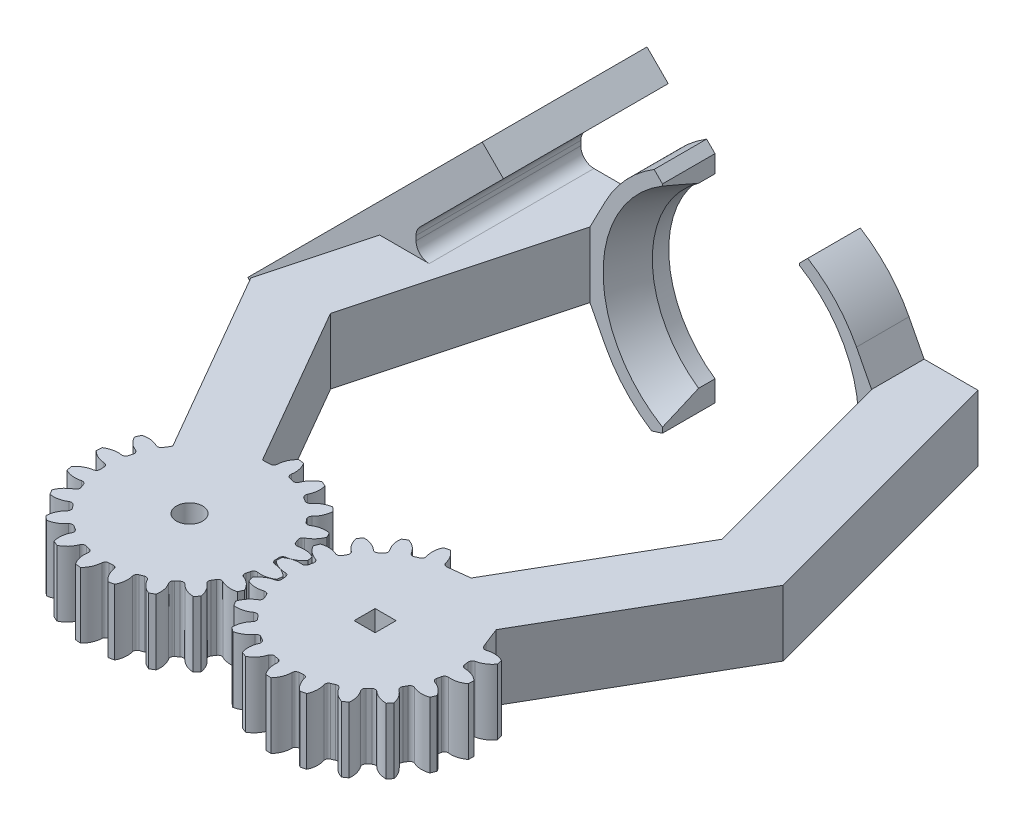
SolidWorks part; units mm, degrees
ref_plane "Front Plane" through (0, 0, 0) normal (0, 0, 1) x (1, 0, 0)
ref_plane "Top Plane" through (0, 0, 0) normal (0, 1, 0) x (1, 0, 0)
ref_plane "Right Plane" through (0, 0, 0) normal (1, 0, 0) x (0, 0, -1)
sketch "Sketch1" plane through (0, 0, 0) normal (0, 1, 0) x (1, 0, 0)
  line L0 (-1.5124, 12.6196) -> (-15.6699, 37.141)
  line L1 (-10.1727, 7.6196) -> (-25.6699, 34.4615)
  line L2 (29.9646, 12.9427) -> (43.9355, 37.141)
  line L3 (38.6794, 8.0371) -> (53.9355, 34.4615)
  line L4 (-13.3963, -7.7344) -> (-13.3913, -7.7315)
  line L5 (-13.1804, -8.0969) -> (-13.6023, -7.3661)
  line L6 (-10.3506, -11.4955) -> (-10.3468, -11.4912)
  line L7 (-10.0332, -11.7735) -> (-10.6603, -11.209)
  line L8 (-6.2917, -14.1314) -> (-6.2894, -14.1261)
  line L9 (-5.904, -14.2977) -> (-6.6748, -13.9546)
  line L10 (-1.6169, -15.384) -> (-1.6163, -15.3783)
  line L11 (-1.1968, -15.4224) -> (-2.0359, -15.3342)
  line L12 (3.2161, -15.1307) -> (3.2149, -15.1251)
  line L13 (3.6276, -15.0374) -> (2.8023, -15.2128)
  line L14 (7.7344, -13.3963) -> (7.7315, -13.3913)
  line L15 (8.0969, -13.1804) -> (7.3661, -13.6023)
  line L16 (11.4955, -10.3506) -> (11.4912, -10.3468)
  line L17 (11.7735, -10.0332) -> (11.209, -10.6603)
  line L18 (14.1314, -6.2917) -> (14.1261, -6.2894)
  line L19 (14.2977, -5.904) -> (13.9546, -6.6748)
  line L20 (15.384, -1.6169) -> (15.3783, -1.6163)
  line L21 (15.4224, -1.1968) -> (15.3342, -2.0359)
  line L22 (15.1307, 3.2161) -> (15.1251, 3.2149)
  line L23 (15.0374, 3.6276) -> (15.2128, 2.8023)
  line L24 (13.3963, 7.7344) -> (13.3913, 7.7315)
  line L25 (13.1804, 8.0969) -> (13.6023, 7.3661)
  line L26 (10.3506, 11.4955) -> (10.3468, 11.4912)
  line L27 (10.0332, 11.7735) -> (10.6603, 11.209)
  line L28 (6.2917, 14.1314) -> (6.2894, 14.1261)
  line L29 (5.904, 14.2977) -> (6.6748, 13.9546)
  line L30 (1.6169, 15.384) -> (1.6163, 15.3783)
  line L31 (1.1968, 15.4224) -> (2.0359, 15.3342)
  line L32 (-14.1314, 6.2917) -> (-14.1261, 6.2894)
  line L33 (-14.2977, 5.904) -> (-13.9546, 6.6748)
  line L34 (-15.384, 1.6169) -> (-15.3783, 1.6163)
  line L35 (-15.4224, 1.1968) -> (-15.3342, 2.0359)
  line L36 (-15.1307, -3.2161) -> (-15.1251, -3.2149)
  line L37 (-15.0374, -3.6276) -> (-15.2128, -2.8023)
  line L38 (-9.6435, -8.1965) -> (-10.0224, -7.7286)
  line L39 (-6.6387, -10.7754) -> (-7.1436, -10.4475)
  line L40 (-2.984, -12.2995) -> (-3.5655, -12.1436)
  line L41 (0.9628, -12.6196) -> (0.3616, -12.6511)
  line L42 (4.8154, -11.7044) -> (4.2533, -11.9202)
  line L43 (8.1965, -9.6435) -> (7.7286, -10.0224)
  line L44 (10.7754, -6.6387) -> (10.4475, -7.1436)
  line L45 (12.2995, -2.984) -> (12.1436, -3.5655)
  line L46 (12.6196, 0.9628) -> (12.6511, 0.3616)
  line L47 (11.7044, 4.8154) -> (11.9202, 4.2533)
  line L48 (9.6435, 8.1965) -> (10.0224, 7.7286)
  line L49 (6.6387, 10.7754) -> (7.1436, 10.4475)
  line L50 (2.984, 12.2995) -> (3.5655, 12.1436)
  line L51 (-0.9628, 12.6196) -> (-0.3616, 12.6511)
  line L52 (-10.7754, 6.6387) -> (-10.4475, 7.1436)
  line L53 (-12.2995, 2.984) -> (-12.1436, 3.5655)
  line L54 (-12.6196, -0.9628) -> (-12.6511, -0.3616)
  line L55 (-11.7044, -4.8154) -> (-11.9202, -4.2533)
  line L56 (43.7132, -0.8096) -> (43.7074, -0.8093)
  line L57 (43.6854, -1.2306) -> (43.7295, -0.388)
  line L58 (42.707, -5.5435) -> (42.7016, -5.5414)
  line L59 (42.5504, -5.9353) -> (42.8528, -5.1476)
  line L60 (40.2871, -9.7348) -> (40.2826, -9.7312)
  line L61 (40.0172, -10.059) -> (40.5481, -9.4033)
  line L62 (36.6905, -12.9732) -> (36.6874, -12.9684)
  line L63 (36.3336, -13.1981) -> (37.0412, -12.7386)
  line L64 (32.2693, -14.9417) -> (32.2678, -14.9361)
  line L65 (31.8603, -15.0453) -> (32.6753, -14.8269)
  line L66 (27.4561, -15.4476) -> (27.4564, -15.4418)
  line L67 (27.0351, -15.4197) -> (27.8777, -15.4639)
  line L68 (22.7221, -14.4413) -> (22.7242, -14.436)
  line L69 (22.3303, -14.2848) -> (23.1181, -14.5871)
  line L70 (18.5308, -12.0215) -> (18.5345, -12.017)
  line L71 (18.2066, -11.7515) -> (18.8623, -12.2825)
  line L72 (15.2925, -8.4249) -> (15.2973, -8.4218)
  line L73 (15.0675, -8.0679) -> (15.5271, -8.7756)
  line L74 (13.324, -4.0036) -> (13.3295, -4.0021)
  line L75 (13.2203, -3.5946) -> (13.4387, -4.4096)
  line L76 (12.8181, 0.8096) -> (12.8238, 0.8093)
  line L77 (12.8459, 1.2306) -> (12.8018, 0.388)
  line L78 (13.8243, 5.5435) -> (13.8297, 5.5414)
  line L79 (13.9809, 5.9353) -> (13.6785, 5.1476)
  line L80 (16.2442, 9.7348) -> (16.2486, 9.7312)
  line L81 (16.5141, 10.059) -> (15.9831, 9.4033)
  line L82 (19.8408, 12.9732) -> (19.8439, 12.9684)
  line L83 (20.1977, 13.1981) -> (19.4901, 12.7386)
  line L84 (24.262, 14.9417) -> (24.2635, 14.9361)
  line L85 (24.671, 15.0453) -> (23.856, 14.8269)
  line L86 (43.2073, 4.0036) -> (43.2018, 4.0021)
  line L87 (43.3109, 3.5946) -> (43.0926, 4.4096)
  line L88 (40.5792, -2.9251) -> (40.7044, -2.3362)
  line L89 (39.0727, -6.5871) -> (39.3737, -6.0656)
  line L90 (36.5082, -9.6042) -> (36.9557, -9.2013)
  line L91 (33.1369, -11.6812) -> (33.687, -11.4363)
  line L92 (29.2888, -12.6148) -> (29.8876, -12.5519)
  line L93 (25.3405, -12.3136) -> (25.9295, -12.4388)
  line L94 (21.6786, -10.807) -> (22.2, -11.1081)
  line L95 (18.6614, -8.2426) -> (19.0643, -8.69)
  line L96 (16.5844, -4.8713) -> (16.8293, -5.4213)
  line L97 (15.6508, -1.0232) -> (15.7138, -1.622)
  line L98 (15.9521, 2.9251) -> (15.8269, 2.3362)
  line L99 (17.4586, 6.5871) -> (17.1576, 6.0656)
  line L100 (20.0231, 9.6042) -> (19.5756, 9.2013)
  line L101 (23.3944, 11.6812) -> (22.8443, 11.4363)
  line L102 (27.2425, 12.6148) -> (26.6437, 12.5519)
  line L103 (39.9469, 4.8713) -> (39.702, 5.4213)
  line L104 (40.8805, 1.0232) -> (40.8175, 1.622)
  line L105 (27.2425, 12.6148) -> (29.9646, 12.9427)
  line L106 (39.702, 5.4213) -> (38.6794, 8.0371)
  line L107 (-10.4475, 7.1436) -> (-10.1727, 7.6196)
  line L108 (-0.9628, 12.6196) -> (-1.5124, 12.6196)
  line L109 (-15.6699, 37.141) -> (-5.3171, 75.778)
  line L110 (-5.3171, 75.778) -> (-14.9764, 78.3662)
  line L111 (-14.9764, 78.3662) -> (-26.4012, 35.7282)
  line L112 (-25.6699, 34.4615) -> (-26.4012, 35.7282)
  line L113 (43.9355, 37.141) -> (33.5828, 75.778)
  line L114 (33.5828, 75.778) -> (43.242, 78.3662)
  line L115 (43.242, 78.3662) -> (54.6668, 35.7282)
  line L116 (53.9355, 34.4615) -> (54.6668, 35.7282)
  circle A0 centre (0, 0) radius 2
  circle A1 centre (28.2656, 0) radius 2
  arc A2 (-13.1804, -8.0969) -> (-10.7748, -7.6007) centre (-12.61, -4.7824) ccw
  arc A3 (-10.0224, -7.7286) -> (-10.7748, -7.6007) centre (-10.4679, -8.0721) ccw
  arc A4 (-11.9698, -5.5309) -> (-13.6023, -7.3661) centre (-10.4467, -8.5294) ccw
  arc A5 (-11.9698, -5.5309) -> (-11.7044, -4.8154) centre (-12.2246, -5.0294) ccw
  arc A6 (-10.0332, -11.7735) -> (-7.8987, -10.5583) centre (-10.515, -8.4451) ccw
  arc A7 (-7.1436, -10.4475) -> (-7.8987, -10.5583) centre (-7.4611, -10.9118) ccw
  arc A8 (-9.6749, -8.9591) -> (-10.6603, -11.209) centre (-7.2997, -11.3401) ccw
  arc A9 (-9.6749, -8.9591) -> (-9.6435, -8.1965) centre (-10.0721, -8.5608) ccw
  arc A10 (-5.904, -14.2977) -> (-4.2494, -12.4824) centre (-7.3907, -11.281) ccw
  arc A11 (-3.5655, -12.1436) -> (-4.2494, -12.4824) centre (-3.724, -12.6833) ccw
  arc A12 (-6.4328, -11.5103) -> (-6.6748, -13.9546) centre (-3.4381, -13.0408) ccw
  arc A13 (-6.4328, -11.5103) -> (-6.6387, -10.7754) centre (-6.9337, -11.2543) ccw
  arc A14 (-1.1968, -15.4224) -> (-0.1841, -13.1846) centre (-3.5429, -13.0127) ccw
  arc A15 (0.3616, -12.6511) -> (-0.1841, -13.1846) centre (0.3776, -13.2134) ccw
  arc A16 (-2.5611, -12.9348) -> (-2.0359, -15.3342) centre (0.76, -13.465) ccw
  arc A17 (-2.5611, -12.9348) -> (-2.984, -12.2995) centre (-3.1166, -12.8461) ccw
  arc A18 (3.6276, -15.0374) -> (3.8991, -12.5962) centre (0.6517, -13.4707) ccw
  arc A19 (4.2533, -11.9202) -> (3.8991, -12.5962) centre (4.4423, -12.45) ccw
  arc A20 (1.5613, -13.0931) -> (2.8023, -15.2128) centre (4.8837, -12.5711) ccw
  arc A21 (1.5613, -13.0931) -> (0.9628, -12.6196) centre (1.0056, -13.1804) ccw
  arc A22 (8.0969, -13.1804) -> (7.6007, -10.7748) centre (4.7824, -12.61) ccw
  arc A23 (7.7286, -10.0224) -> (7.6007, -10.7748) centre (8.0721, -10.4679) ccw
  arc A24 (5.5309, -11.9698) -> (7.3661, -13.6023) centre (8.5294, -10.4467) ccw
  arc A25 (5.5309, -11.9698) -> (4.8154, -11.7044) centre (5.0294, -12.2246) ccw
  arc A26 (11.7735, -10.0332) -> (10.5583, -7.8987) centre (8.4451, -10.515) ccw
  arc A27 (10.4475, -7.1436) -> (10.5583, -7.8987) centre (10.9118, -7.4611) ccw
  arc A28 (8.9591, -9.6749) -> (11.209, -10.6603) centre (11.3401, -7.2997) ccw
  arc A29 (8.9591, -9.6749) -> (8.1965, -9.6435) centre (8.5608, -10.0721) ccw
  arc A30 (14.2977, -5.904) -> (12.4824, -4.2494) centre (11.281, -7.3907) ccw
  arc A31 (12.1436, -3.5655) -> (12.4824, -4.2494) centre (12.6833, -3.724) ccw
  arc A32 (11.5103, -6.4328) -> (13.9546, -6.6748) centre (13.0408, -3.4381) ccw
  arc A33 (11.5103, -6.4328) -> (10.7754, -6.6387) centre (11.2543, -6.9337) ccw
  arc A34 (15.4224, -1.1968) -> (13.1846, -0.1841) centre (13.0127, -3.5429) ccw
  arc A35 (12.6511, 0.3616) -> (13.1846, -0.1841) centre (13.2134, 0.3776) ccw
  arc A36 (12.9348, -2.5611) -> (15.3342, -2.0359) centre (13.465, 0.76) ccw
  arc A37 (12.9348, -2.5611) -> (12.2995, -2.984) centre (12.8461, -3.1166) ccw
  arc A38 (15.0374, 3.6276) -> (12.5962, 3.8991) centre (13.4707, 0.6517) ccw
  arc A39 (11.9202, 4.2533) -> (12.5962, 3.8991) centre (12.45, 4.4423) ccw
  arc A40 (13.0931, 1.5613) -> (15.2128, 2.8023) centre (12.5711, 4.8837) ccw
  arc A41 (13.0931, 1.5613) -> (12.6196, 0.9628) centre (13.1804, 1.0056) ccw
  arc A42 (13.1804, 8.0969) -> (10.7748, 7.6007) centre (12.61, 4.7824) ccw
  arc A43 (10.0224, 7.7286) -> (10.7748, 7.6007) centre (10.4679, 8.0721) ccw
  arc A44 (11.9698, 5.5309) -> (13.6023, 7.3661) centre (10.4467, 8.5294) ccw
  arc A45 (11.9698, 5.5309) -> (11.7044, 4.8154) centre (12.2246, 5.0294) ccw
  arc A46 (10.0332, 11.7735) -> (7.8987, 10.5583) centre (10.515, 8.4451) ccw
  arc A47 (7.1436, 10.4475) -> (7.8987, 10.5583) centre (7.4611, 10.9118) ccw
  arc A48 (9.6749, 8.9591) -> (10.6603, 11.209) centre (7.2997, 11.3401) ccw
  arc A49 (9.6749, 8.9591) -> (9.6435, 8.1965) centre (10.0721, 8.5608) ccw
  arc A50 (5.904, 14.2977) -> (4.2494, 12.4824) centre (7.3907, 11.281) ccw
  arc A51 (3.5655, 12.1436) -> (4.2494, 12.4824) centre (3.724, 12.6833) ccw
  arc A52 (6.4328, 11.5103) -> (6.6748, 13.9546) centre (3.4381, 13.0408) ccw
  arc A53 (6.4328, 11.5103) -> (6.6387, 10.7754) centre (6.9337, 11.2543) ccw
  arc A54 (1.1968, 15.4224) -> (0.1841, 13.1846) centre (3.5429, 13.0127) ccw
  arc A55 (-0.3616, 12.6511) -> (0.1841, 13.1846) centre (-0.3776, 13.2134) ccw
  arc A56 (2.5611, 12.9348) -> (2.0359, 15.3342) centre (-0.76, 13.465) ccw
  arc A57 (2.5611, 12.9348) -> (2.984, 12.2995) centre (3.1166, 12.8461) ccw
  arc A58 (-14.2977, 5.904) -> (-12.4824, 4.2494) centre (-11.281, 7.3907) ccw
  arc A59 (-12.1436, 3.5655) -> (-12.4824, 4.2494) centre (-12.6833, 3.724) ccw
  arc A60 (-11.5103, 6.4328) -> (-13.9546, 6.6748) centre (-13.0408, 3.4381) ccw
  arc A61 (-11.5103, 6.4328) -> (-10.7754, 6.6387) centre (-11.2543, 6.9337) ccw
  arc A62 (-15.4224, 1.1968) -> (-13.1846, 0.1841) centre (-13.0127, 3.5429) ccw
  arc A63 (-12.6511, -0.3616) -> (-13.1846, 0.1841) centre (-13.2134, -0.3776) ccw
  arc A64 (-12.9348, 2.5611) -> (-15.3342, 2.0359) centre (-13.465, -0.76) ccw
  arc A65 (-12.9348, 2.5611) -> (-12.2995, 2.984) centre (-12.8461, 3.1166) ccw
  arc A66 (-15.0374, -3.6276) -> (-12.5962, -3.8991) centre (-13.4707, -0.6517) ccw
  arc A67 (-11.9202, -4.2533) -> (-12.5962, -3.8991) centre (-12.45, -4.4423) ccw
  arc A68 (-13.0931, -1.5613) -> (-15.2128, -2.8023) centre (-12.5711, -4.8837) ccw
  arc A69 (-13.0931, -1.5613) -> (-12.6196, -0.9628) centre (-13.1804, -1.0056) ccw
  arc A70 (41.3167, -1.8806) -> (43.6854, -1.2306) centre (41.6724, 1.4636) ccw
  arc A71 (41.3167, -1.8806) -> (40.7044, -2.3362) centre (41.2572, -2.44) ccw
  arc A72 (43.7295, -0.388) -> (41.4418, 0.5061) centre (41.446, -2.857) ccw
  arc A73 (40.8805, 1.0232) -> (41.4418, 0.5061) centre (41.4411, 1.0686) ccw
  arc A74 (40.0968, -5.8216) -> (42.5504, -5.9353) centre (41.4685, -2.7509) ccw
  arc A75 (40.0968, -5.8216) -> (39.3737, -6.0656) centre (39.8674, -6.3352) ccw
  arc A76 (42.8528, -5.1476) -> (40.9533, -3.5903) centre (39.918, -6.7901) ccw
  arc A77 (40.5792, -2.9251) -> (40.9533, -3.5903) centre (41.1265, -3.0551) ccw
  arc A78 (37.7188, -9.1927) -> (40.0172, -10.059) centre (39.9722, -6.6962) ccw
  arc A79 (37.7188, -9.1927) -> (36.9557, -9.2013) centre (37.3419, -9.6103) ccw
  arc A80 (40.5481, -9.4033) -> (39.2229, -7.3353) centre (37.2494, -10.0586) ccw
  arc A81 (39.0727, -6.5871) -> (39.2229, -7.3353) centre (39.553, -6.8798) ccw
  arc A82 (34.4154, -11.664) -> (36.3336, -13.1981) centre (37.33, -9.986) ccw
  arc A83 (34.4154, -11.664) -> (33.687, -11.4363) centre (33.9279, -11.9446) ccw
  arc A84 (37.0412, -12.7386) -> (36.4199, -10.3623) centre (33.7015, -12.3424) ccw
  arc A85 (36.5082, -9.6042) -> (36.4199, -10.3623) centre (36.8745, -10.0311) ccw
  arc A86 (30.51, -12.9935) -> (31.8603, -15.0453) centre (33.8006, -12.2983) ccw
  arc A87 (30.51, -12.9935) -> (29.8876, -12.5519) centre (29.9597, -13.1097) ccw
  arc A88 (32.6753, -14.8269) -> (32.8187, -12.3749) centre (29.6214, -13.4181) ccw
  arc A89 (33.1369, -11.6812) -> (32.8187, -12.3749) centre (33.3534, -12.2004) ccw
  arc A90 (26.385, -13.0511) -> (27.0351, -15.4197) centre (29.7293, -13.4068) ccw
  arc A91 (26.385, -13.0511) -> (25.9295, -12.4388) centre (25.8256, -12.9916) ccw
  arc A92 (27.8777, -15.4639) -> (28.7718, -13.1762) centre (25.4086, -13.1803) ccw
  arc A93 (29.2888, -12.6148) -> (28.7718, -13.1762) centre (29.3343, -13.1755) ccw
  arc A94 (22.444, -11.8312) -> (22.3303, -14.2848) centre (25.5147, -13.2029) ccw
  arc A95 (22.444, -11.8312) -> (22.2, -11.1081) centre (21.9304, -11.6017) ccw
  arc A96 (23.1181, -14.5871) -> (24.6753, -12.6877) centre (21.4755, -11.6524) ccw
  arc A97 (25.3405, -12.3136) -> (24.6753, -12.6877) centre (25.2105, -12.8609) ccw
  arc A98 (19.0729, -9.4531) -> (18.2066, -11.7515) centre (21.5695, -11.7066) ccw
  arc A99 (19.0729, -9.4531) -> (19.0643, -8.69) centre (18.6554, -9.0762) ccw
  arc A100 (18.8623, -12.2825) -> (20.9304, -10.9573) centre (18.2071, -8.9838) ccw
  arc A101 (21.6786, -10.807) -> (20.9304, -10.9573) centre (21.3858, -11.2873) ccw
  arc A102 (16.6017, -6.1498) -> (15.0675, -8.0679) centre (18.2796, -9.0644) ccw
  arc A103 (16.6017, -6.1498) -> (16.8293, -5.4213) centre (16.321, -5.6623) ccw
  arc A104 (15.5271, -8.7756) -> (17.9034, -8.1542) centre (15.9232, -5.4358) ccw
  arc A105 (18.6614, -8.2426) -> (17.9034, -8.1542) centre (18.2346, -8.6089) ccw
  arc A106 (15.2722, -2.2444) -> (13.2203, -3.5946) centre (15.9673, -5.5349) ccw
  arc A107 (15.2722, -2.2444) -> (15.7138, -1.622) centre (15.1559, -1.6941) ccw
  arc A108 (13.4387, -4.4096) -> (15.8908, -4.553) centre (14.8475, -1.3558) ccw
  arc A109 (16.5844, -4.8713) -> (15.8908, -4.553) centre (16.0652, -5.0878) ccw
  arc A110 (15.2146, 1.8806) -> (12.8459, 1.2306) centre (14.8589, -1.4636) ccw
  arc A111 (15.2146, 1.8806) -> (15.8269, 2.3362) centre (15.274, 2.44) ccw
  arc A112 (12.8018, 0.388) -> (15.0895, -0.5061) centre (15.0853, 2.857) ccw
  arc A113 (15.6508, -1.0232) -> (15.0895, -0.5061) centre (15.0902, -1.0686) ccw
  arc A114 (16.4345, 5.8216) -> (13.9809, 5.9353) centre (15.0628, 2.7509) ccw
  arc A115 (16.4345, 5.8216) -> (17.1576, 6.0656) centre (16.6639, 6.3352) ccw
  arc A116 (13.6785, 5.1476) -> (15.578, 3.5903) centre (16.6133, 6.7901) ccw
  arc A117 (15.9521, 2.9251) -> (15.578, 3.5903) centre (15.4048, 3.0551) ccw
  arc A118 (18.8125, 9.1927) -> (16.5141, 10.059) centre (16.559, 6.6962) ccw
  arc A119 (18.8125, 9.1927) -> (19.5756, 9.2013) centre (19.1894, 9.6103) ccw
  arc A120 (15.9831, 9.4033) -> (17.3084, 7.3353) centre (19.2818, 10.0586) ccw
  arc A121 (17.4586, 6.5871) -> (17.3084, 7.3353) centre (16.9783, 6.8798) ccw
  arc A122 (22.1159, 11.664) -> (20.1977, 13.1981) centre (19.2012, 9.986) ccw
  arc A123 (22.1159, 11.664) -> (22.8443, 11.4363) centre (22.6034, 11.9446) ccw
  arc A124 (19.4901, 12.7386) -> (20.1114, 10.3623) centre (22.8298, 12.3424) ccw
  arc A125 (20.0231, 9.6042) -> (20.1114, 10.3623) centre (19.6567, 10.0311) ccw
  arc A126 (26.0212, 12.9935) -> (24.671, 15.0453) centre (22.7307, 12.2983) ccw
  arc A127 (26.0212, 12.9935) -> (26.6437, 12.5519) centre (26.5716, 13.1097) ccw
  arc A128 (23.856, 14.8269) -> (23.7126, 12.3749) centre (26.9099, 13.4181) ccw
  arc A129 (23.3944, 11.6812) -> (23.7126, 12.3749) centre (23.1779, 12.2004) ccw
  arc A130 (41.2591, 2.2444) -> (43.3109, 3.5946) centre (40.5639, 5.5349) ccw
  arc A131 (41.2591, 2.2444) -> (40.8175, 1.622) centre (41.3754, 1.6941) ccw
  arc A132 (43.0926, 4.4096) -> (40.6405, 4.553) centre (41.6837, 1.3558) ccw
  arc A133 (39.9469, 4.8713) -> (40.6405, 4.553) centre (40.466, 5.0878) ccw
extrude "Boss-Extrude1" add sketch "Sketch1" along normal blind 10 contours A133 L103 L106 L3 L116 L115 L114 L113 L2 L105 L102 A127 A126 L85 A128 A129 L101 A123 A122 L83 A124 A125 L100 A119 A118 L81 A120 A121 L99 A115 A114 L79 A116 A117 L98 A111 A110 L77 A112 A113 L97 A107 A106 L75 A108 | A69 A68 L37 A66 A67 L55 A5 A4 L5 A2 A3 L38 A9 A8 L7 A6 A7 L39 A13 A12 L9 A10 A11 L40 A17 A16 L11 A14 A15 L41 A21 A20 L13 A18 A19 L42 A25 A24 L15 A22 A23 L43 A29 A28 region at (-8.072, 0, -23.4532) region at (36.3461, 0, -23.5032)
sketch "Sketch2" plane through (0, 0, 0) normal (0, -1, 0) x (1, 0, 0)
  line L1 (-7.3171, -75.778) -> (-7.3171, -68.3139)
  line L2 (-15.6699, -37.141) -> (-5.3171, -75.778) construction
  line L3 (-7.3171, -75.778) -> (-7.3171, -76.3139)
  line L4 (-5.3171, -75.778) -> (-14.9764, -78.3662) construction
  line L5 (-7.3171, -68.3139) -> (-5.3171, -75.778)
  line L6 (-7.3171, -76.3139) -> (-5.3171, -75.778)
  line L8 (35.5828, -68.3139) -> (35.5828, -76.3139)
  line L9 (43.9355, -37.141) -> (33.5828, -75.778) construction
  line L11 (33.5828, -75.778) -> (43.242, -78.3662) construction
  line L15 (35.5828, -76.3139) -> (33.5828, -75.778)
  line L16 (33.5828, -75.778) -> (35.5828, -68.3139)
  dimension "D1" = 8
  dimension "D3" = 8
extrude "Cut-Extrude1" cut sketch "Sketch2" against normal through all
sketch "Sketch4" plane through (-7.3171, 0, 0) normal (1, 0, 0) x (0, 0, -1)
  line L0 (68.3139, 5) -> (68.3139, 25)
  line L1 (68.3139, 10) -> (68.3139, 0) construction
  line L2 (68.3139, 5) -> (68.3139, -15)
  line L4 (76.3139, 0) -> (76.3139, -15)
  line L5 (76.3139, -15) -> (68.3139, -15)
  line L7 (76.3139, 10) -> (76.3139, 25)
  line L8 (76.3139, 25) -> (68.3139, 25)
  line L9 (76.3139, 0) -> (76.3139, 10)
  dimension "D1" = 20
  dimension "D2" = 20
extrude "Boss-Extrude2" add sketch "Sketch4" along normal blind 20.5
sketch "Sketch5" plane through (35.5828, 0, 0) normal (-1, 0, 0) x (0, 0, 1)
  line L1 (-68.3139, 5) -> (-68.3139, 35)
  line L2 (-68.3139, 10) -> (-68.3139, 0) construction
  line L3 (-76.3139, 5) -> (-76.3139, -25)
  line L4 (-76.3139, 10) -> (-76.3139, 0) construction
  line L6 (-68.3139, 5) -> (-68.3139, -25)
  line L8 (-76.3139, 5) -> (-76.3139, 35)
  line L10 (-68.3139, 35) -> (-76.3139, 35)
  line L12 (-76.3139, -25) -> (-68.3139, -25)
  dimension "D1" = 30
  dimension "D2" = 30
  dimension "D3" = 30
  dimension "D4" = 30
sketch "Sketch6" plane through (0, 0, -68.3139) normal (0, 0, 1) x (1, 0, 0)
  line L0 (13.1829, 25) -> (13.1829, -15) construction
  line L3 (-7.3171, 0) -> (-5.015, -4.4385)
  line L4 (-7.3171, 10) -> (-5.015, 14.4385)
  line L7 (-7.3171, 0) -> (-7.3171, 10)
  line L9 (8.7279, 25.0101) -> (8.7279, 20.8872)
  line L10 (8.7279, -10.8872) -> (8.7279, -15.0101)
  line L12 (-7.3171, 25) -> (13.1829, 25)
  line L13 (-7.3171, 25) -> (-7.3171, -15)
  line L14 (-7.3171, -15) -> (13.1829, -15)
  line L15 (13.1829, 25) -> (13.1829, -15)
  arc A0 (8.7279, 20.8872) -> (8.7279, -10.8872) centre (13.1829, 5) ccw
  arc A2 (-5.015, -4.4385) -> (8.7279, -15.0101) centre (13.1829, 5) ccw
  arc A3 (8.7279, 25.0101) -> (-5.015, 14.4385) centre (13.1829, 5) ccw
  line M5 (-7.3171, 25) -> (-7.3171, 10)
  line M7 (-7.3171, 0) -> (-7.3171, -15)
  line M8 (-7.3171, -15) -> (13.1829, -15)
  line M9 (13.1829, -15) -> (13.1829, 25)
  line M10 (13.1829, 25) -> (-7.3171, 25)
  dimension "D1" = 33
extrude "Cut-Extrude9" cut sketch "Sketch6" against normal blind 20.5 contours A2 L3 M7 M8 | L9 A0 L10 M8 M9 M10 | A3 L12 L4 M5 region at (-3.0986, -10.7161, -68.3139) region at (-3.0986, 20.7161, -68.3139) region at (6.5177, 5, -68.3139)
extrude "Boss-Extrude3" add sketch "Sketch5" along normal blind 20.5
sketch "Sketch9" plane through (0, 0, -68.3139) normal (0, 0, 1) x (1, 0, 0)
  line L13 (15.0828, -25) -> (15.0828, 35) construction
  line L14 (35.5828, 10) -> (35.5828, 0)
  line L24 (35.5828, 10) -> (35.5828, 0)
  line L25 (35.5828, 0) -> (33.2807, -4.4385)
  line L26 (35.5828, 10) -> (33.2807, 14.4385)
  line L27 (19.5828, 20.8745) -> (19.5828, 25)
  line L28 (19.5828, -10.8745) -> (19.5828, -15)
  arc A7 (19.5828, -10.8745) -> (19.5828, 20.8745) centre (15.0828, 5) ccw
  arc A8 (19.5828, -15) -> (33.2807, -4.4385) centre (15.0828, 5) ccw
  arc A9 (19.5828, -15) -> (33.2807, -4.4385) centre (15.0828, 5) ccw
  arc A10 (33.2807, 14.4385) -> (19.5828, 25) centre (15.0828, 5) ccw
  line M5 (35.5828, -25) -> (35.5828, 0)
  line M7 (35.5828, 10) -> (35.5828, 35)
  line M8 (35.5828, 35) -> (15.0828, 35)
  line M9 (15.0828, 35) -> (15.0828, -25)
  line M10 (15.0828, -25) -> (35.5828, -25)
  dimension "D1" = 33
extrude "Cut-Extrude32" cut sketch "Sketch9" against normal blind 20.5 contours A10 L26 L25 A8 L28 A7 L27 M7 M8 M9 M10 M5 region at (24.6582, 5, -68.3139)
sketch "Sketch10" plane through (0, 0, 0) normal (0, -1, 0) x (1, 0, 0)
  line L0 (-7.3171, -76.3139) -> (-15.5263, -76.3139)
  line L1 (-14.9764, -78.3662) -> (-26.4012, -35.7282) construction
  line L2 (-15.5263, -76.3139) -> (-14.9764, -78.3662)
  line L3 (-14.9764, -78.3662) -> (-7.3171, -76.3139)
  line L4 (35.5828, -76.3139) -> (43.7919, -76.3139)
  line L5 (43.242, -78.3662) -> (54.6668, -35.7282) construction
  line L6 (43.7919, -76.3139) -> (43.242, -78.3662)
  line L7 (43.242, -78.3662) -> (35.5828, -76.3139)
extrude "Cut-Extrude33" cut sketch "Sketch10" against normal blind 20.5
sketch "Sketch16" plane through (0, 10, 0) normal (0, 1, 0) x (1, 0, 0)
  line L1 (26.6656, -1.6) -> (29.8656, -1.6)
  line L2 (26.6656, -1.6) -> (26.6656, 1.6)
  line L3 (26.6656, 1.6) -> (29.8656, 1.6)
  line L4 (29.8656, -1.6) -> (29.8656, 1.6)
  line L5 (26.6656, -1.6) -> (29.8656, 1.6) construction
  line L6 (26.6656, 1.6) -> (29.8656, -1.6) construction
  circle A0 centre (28.2656, 0) radius 2
  point P0 (28.2656, 0)
  dimension "D1" = 3.2
  dimension "D2" = 3.2
extrude "Boss-Extrude7" add sketch "Sketch16" against normal blind 5 contours L3 A0 | L4 A0 | L1 A0 | L2 A0 region at (28.2656, 10, 1.7615) region at (26.5042, 10, 0) region at (30.0271, 10, 0) region at (28.2656, 10, -1.7615)
sketch "Sketch17" plane through (0, 10, 0) normal (0, 1, 0) x (1, 0, 0)
  line L1 (26.6656, -1.6) -> (29.8656, -1.6)
  line L2 (26.6656, -1.6) -> (26.6656, 1.6)
  line L3 (26.6656, 1.6) -> (29.8656, 1.6)
  line L4 (29.8656, -1.6) -> (29.8656, 1.6)
  line L5 (26.6656, -1.6) -> (29.8656, 1.6) construction
  line L6 (26.6656, 1.6) -> (29.8656, -1.6) construction
  circle A0 centre (28.2656, 0) radius 2
  point P0 (28.2656, 0)
  dimension "D1" = 3.2
  dimension "D2" = 3.2
extrude "Cut-Extrude35" cut sketch "Sketch17" against normal blind 5 contours A0 L3 L2 | A0 L4 L3 | A0 L1 L4 | A0 L2 L1 region at (26.7926, 10, 1.4731) region at (29.7387, 10, 1.4731) region at (26.7926, 10, -1.4731) region at (29.7387, 10, -1.4731)
sketch "Sketch18" plane through (0, 0, -68.3139) normal (0, 0, 1) x (1, 0, 0)
  line L0 (19.5828, 25) -> (19.5828, 20.8745)
  line L2 (3.7279, -8.5223) -> (3.7279, -13.1894)
  line L6 (24.5828, -13.1659) -> (24.5828, -8.4907)
  line L8 (19.5828, -10.8745) -> (19.5828, -15)
  line L9 (24.5828, 25) -> (24.5828, 14.9269)
  line L11 (3.7279, 23.1823) -> (3.7279, 14.9269)
  line L12 (3.7279, 14.9269) -> (10.8868, 14.9269)
  line L13 (10.8868, 23.1823) -> (10.8868, 14.9269)
  line L15 (3.7279, 23.1823) -> (3.7279, 32.214)
  line L16 (3.7279, 32.214) -> (10.8868, 32.214)
  line L17 (10.8868, 23.1823) -> (10.8868, 32.214)
  line L18 (3.7279, -8.5223) -> (11.4152, -8.5223)
  line L19 (3.7279, -8.5223) -> (3.7279, -24.2522)
  line L20 (3.7279, -24.2522) -> (11.4152, -24.2522)
  line L21 (11.4152, -8.5223) -> (11.4152, -24.2522)
  line L22 (19.5828, -15) -> (24.5828, -15)
  line L23 (19.5828, -15) -> (19.5828, -3.87)
  line L24 (19.5828, -3.87) -> (24.5828, -3.87)
  line L25 (24.5828, -15) -> (24.5828, -3.87)
  line L26 (19.5828, 25) -> (24.5828, 25)
  line L27 (19.5828, 25) -> (19.5828, 14.9269)
  line L28 (19.5828, 14.9269) -> (24.5828, 14.9269)
  arc A1 (-5.015, -4.4385) -> (8.6829, -15) centre (13.1829, 5) ccw construction
  arc M10 (19.5828, -15) -> (33.2807, -4.4385) centre (15.0828, 5) ccw
  arc M14 (33.2807, 14.4385) -> (19.5828, 25) centre (15.0828, 5) ccw
  line M15 (19.5828, 25) -> (19.5828, 20.8745)
  arc M16 (19.5828, 20.8745) -> (19.5828, -10.8745) centre (15.0828, 5) cw
  line M17 (19.5828, -10.8745) -> (19.5828, -15)
extrude "Cut-Extrude36" cut sketch "Sketch18" against normal through all contours M16 M14 M15 | L6 M10 M16 M17 | L2 | L15 L16 L17 L13 L12 L11 | L23 L22 L25 L24 | L26 L9 L28 L27 region at (22.1345, 22.0091, -68.3139) region at (22.1345, -12.0091, -68.3139) region at (7.5716, -16.3873, -68.3139)
chamfer "Chamfer4" distance 2 angle 70 1 edges at (31.5828, 5, -68.3139) first distance on face at (30.55, 5, -68.3139)
chamfer "Chamfer5" distance 2 angle 70 1 edges at (-3.3171, 5, -68.3139) first distance on face at (-2.2687, 5, -68.3139)
sketch "Sketch19" plane through (0, 10, 0) normal (0, 1, 0) x (1, 0, 0)
  line L0 (-15.5263, 76.3139) -> (-22.2518, 76.3139)
  line L1 (-22.2518, 76.3139) -> (-22.2518, 51.2139)
  line L2 (-15.5263, 76.3139) -> (-26.4012, 35.7282) construction
  line L3 (-15.5263, 76.3139) -> (-22.2518, 51.2139)
  dimension "D1" = 25.1
extrude "Boss-Extrude8" add sketch "Sketch19" against normal blind 10
sketch "Sketch27" plane through (0, 0, -76.3139) normal (0, 0, -1) x (-1, 0, 0)
  line L0 (22.2518, 10) -> (20.2518, 10)
  line L1 (22.2518, 10) -> (7.3171, 10) construction
  line L2 (20.2518, 10) -> (22.2518, 8)
  line L3 (22.2518, 0) -> (22.2518, 10) construction
  dimension "D1" = 2
  dimension "D2" = 2
extrude "Cut-Extrude39" cut sketch "Sketch27" against normal blind 25.1 and the other way through all
sketch "Sketch28" plane through (-15.1259, 15.1259, 0) normal (-0.7071, 0.7071, 0) x (0, 0, 1)
  line L0 (-76.3139, -8.6633) -> (-76.3139, 16.5867)
  line L3 (-51.2139, -8.6633) -> (-51.2139, -33.9133)
  line L4 (-76.3139, -10.0775) -> (-76.3139, -7.2491) construction
  line L5 (-76.3139, 19.0334) -> (-76.3139, 6.6634) construction
  line L7 (-76.3139, 16.5867) -> (-51.2139, 16.5867)
  line L8 (-76.3139, 16.5867) -> (-76.3139, -33.9133)
  line L9 (-76.3139, -33.9133) -> (-51.2139, -33.9133)
  line L10 (-51.2139, 16.5867) -> (-51.2139, -33.9133)
  line M4 (-76.3139, -7.2491) -> (-76.3139, -10.0775)
  line M5 (-76.3139, -10.0775) -> (-51.2139, -10.0775)
  line M6 (-51.2139, -10.0775) -> (-51.2139, -7.2491)
  line M7 (-51.2139, -7.2491) -> (-76.3139, -7.2491)
  dimension "D1" = 25.25
  dimension "D2" = 25.25
extrude "Boss-Extrude11" add sketch "Sketch28" along normal blind 4.57 contours L10 L7 L0 M7 | L8 L9 L3 M5 | M7 M4 M5 M6 region at (-21.2518, 9, -63.7639) region at (-11.8246, 18.4272, -63.7639) region at (-30.679, -0.4272, -63.7639)
sketch "Sketch29" plane through (-18.3574, 18.3574, 0) normal (-0.7071, 0.7071, 0) x (0, 0, 1)
  line L0 (-76.3139, -33.9133) -> (-76.3139, 16.5867) construction
  line L1 (-51.2139, 16.5867) -> (-51.2139, -33.9133) construction
  line L2 (-76.3139, -33.9133) -> (-51.2139, -33.9133) construction
  line L3 (-76.3139, 16.5867) -> (-51.2139, 16.5867) construction
  circle A0 centre (-70.1139, 10.3867) radius 2.1
  circle A1 centre (-57.4139, 10.3867) radius 2.1
  circle A2 centre (-70.1139, -27.7133) radius 2.1
  circle A3 centre (-57.4139, -27.7133) radius 2.1
  point P8 (0, 0)
  point P13 (0, 0)
  point P14 (0, 0)
  point P15 (0, 0)
  point P16 (0, 0)
  point P17 (0, 0)
  dimension "D1" = 4.2
  dimension "D2" = 4.2
  dimension "D3" = 4.2
  dimension "D4" = 4.2
  dimension "D5" = 6.2
  dimension "D6" = 6.2
  dimension "D7" = 6.2
  dimension "D8" = 6.2
extrude "Cut-Extrude40" cut sketch "Sketch29" against normal blind 4.57
chamfer "Chamfer9" distance 5 angle 45 2 edges at (-20.2518, 10, -63.7639) (-22.2518, 8, -63.7639) first distance on face at (-9.2663, 20.9855, -57.4139) first distance on face at (-22.2518, 4, -63.7639)
chamfer "Chamfer10" distance 5 angle 45 1 edges at (-24.7518, 5.5, -63.7639)
fillet "Fillet3" radius 2 2 edges at (-16.7163, 10, -63.7639) (-16.7163, 13.5355, -63.7639)
fillet "Fillet4" radius 2 2 edges at (-28.2873, 1.9645, -63.7639) (-22.2518, 1.9645, -63.7639)
chamfer "Chamfer12" distance 2 angle 45 2 edges at (3.7279, -13.1894, -72.3139) (3.7279, 23.1894, -72.3139) first distance on face at (-0.9815, -9.1515, -72.3139) first distance on face at (3.7279, 21.1029, -72.0634)
chamfer "Chamfer13" distance 2 angle 45 2 edges at (24.5828, 23.1659, -72.3139) (24.5828, -13.1659, -72.3139) first distance on face at (24.5828, 20.5992, -73.1624) first distance on face at (29.2673, -9.1367, -72.3139)
